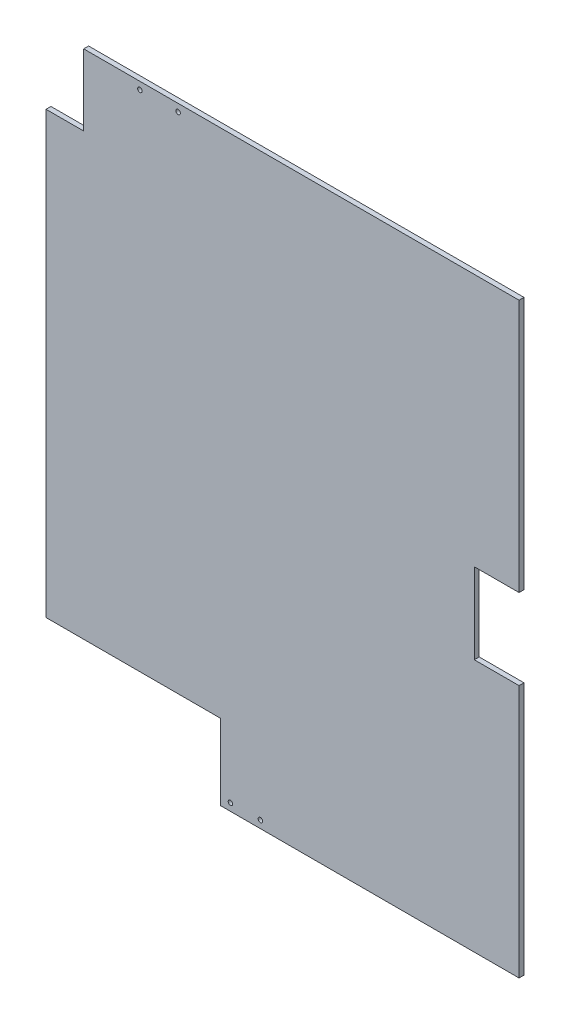
SolidWorks part; units mm, degrees
material "Balsa"
ref_plane "Front Plane" through (0, 0, 0) normal (0, 0, 1) x (1, 0, 0)
ref_plane "Top Plane" through (0, 0, 0) normal (0, 1, 0) x (1, 0, 0)
ref_plane "Right Plane" through (0, 0, 0) normal (1, 0, 0) x (0, 0, -1)
sketch "Sketch1" plane through (0, 0, 0) normal (0, 0, 1) x (1, 0, 0)
  line L0 (-5.7823, -13) -> (25.5, -13)
  line L2 (-5.7823, 1) -> (-5.7823, -13)
  line L5 (24.5, -14) -> (-24.5, -14) construction
  line L6 (342.5, -265) -> (342.5, 30)
  line L7 (-5.8246, -265) -> (65.6329, -265)
  line L8 (-5.8246, -265) -> (-5.8246, -225)
  line L11 (-5.8246, -265) -> (65.6329, -225) construction
  line L12 (-5.8246, -225) -> (65.6329, -265) construction
  line L15 (342.5, -265) -> (25.5, -265)
  line L16 (25.5, 1) -> (25.5, -265)
  line L17 (-5.8246, -225) -> (25.5, -225)
  line L18 (-24.5, -224) -> (24.5, -224) construction
  line L19 (-5.7823, 1) -> (25.5, 1)
  line L20 (24.5, -224) -> (24.5, -14) construction
  line L21 (-85.1981, 31) -> (50.7481, 31) construction
  line L23 (25.5, 1) -> (25.5, 30)
  line L24 (25.5, 30) -> (342.5, 30)
  line L28 (26.2777, -266) -> (-26.2882, -266) construction
  line L30 (-63.4467, 81) -> (255.5737, 81) construction
  line L31 (50.7481, 30) -> (342.5, 30)
  line L32 (50.7481, 30) -> (50.7481, 77.7)
  line L33 (50.7481, 77.7) -> (342.5, 77.7)
  line L34 (342.5, 30) -> (342.5, 77.7)
  line L35 (50.7481, 30) -> (342.5, 77.7) construction
  line L36 (50.7481, 77.7) -> (342.5, 30) construction
  line L37 (255.5737, -319) -> (-63.4467, -319) construction
  line L38 (342.5, -265) -> (142.5, -265)
  line L39 (342.5, -265) -> (342.5, -315.7)
  line L40 (342.5, -315.7) -> (142.5, -315.7)
  line L41 (142.5, -265) -> (142.5, -315.7)
  line L42 (342.5, -265) -> (142.5, -315.7) construction
  line L43 (342.5, -315.7) -> (142.5, -265) construction
  line L44 (50.7481, 31) -> (50.7481, -269) construction
  point P4 (32.4695, -6)
  point P10 (29.9042, -245)
  point P15 (48.1318, -132)
  point P24 (48.1318, 15.5)
  point P36 (196.6241, 53.85)
  point P42 (242.5, -290.35)
  dimension "D1" = 1
  dimension "D2" = 1
  dimension "D3" = 1
  dimension "D4" = 1
  dimension "D5" = 1
  dimension "D6" = 31.3246
  dimension "D7" = 317
  dimension "D8" = 3.3
  dimension "D9" = 200
  dimension "D10" = 3.3
extrude "Boss-Extrude1" add sketch "Sketch1" along normal blind 3.3 contours L24 L23 L16 L7 L15 L6 | L19 L2 L0 L16 | L17 L8 L7 L16 | L24 L34 L33 L32 | L15 L41 L40 L39 region at (9.8589, -6, 0) region at (184, -117.5, 0) region at (9.8377, -245, 0) region at (196.6241, 53.85, 0) region at (242.5, -290.35, 0)
sketch "Sketch2" plane through (0, 0, 0) normal (0, 0, -1) x (-1, 0, 0)
  circle A0 centre (-113.9984, 72.7) radius 1.5
  circle A1 centre (-88.397, 72.7) radius 1.5
  circle A2 centre (-169.1689, -310.7) radius 1.5
  circle A3 centre (-149.0844, -310.7) radius 1.5
  dimension "D1" = 3
  dimension "D2" = 3
  dimension "D3" = 3
  dimension "D4" = 3
extrude "Cut-Extrude1" cut sketch "Sketch2" against normal through all
sketch "Sketch3" plane through (119.3915, 0, 256.0358) normal (0.4226, 0, 0.9063) x (0.9063, 0, -0.4226)
  line L1 (293.4595, -146) -> (268.9595, -146)
  line L2 (293.4595, -146) -> (293.4595, -92)
  line L3 (293.4595, -92) -> (268.9595, -92)
  line L4 (268.9595, -146) -> (268.9595, -92)
  line L5 (293.4595, -146) -> (268.9595, -92) construction
  line L6 (293.4595, -92) -> (268.9595, -146) construction
  point P4 (281.2095, -119)
sketch "Sketch4" plane through (0, 0, 0) normal (0, 0, -1) x (-1, 0, 0)
  line L1 (-342.5, -92) -> (-312.5, -92)
  line L2 (-342.5, -92) -> (-342.5, -146)
  line L3 (-342.5, -146) -> (-312.5, -146)
  line L4 (-312.5, -92) -> (-312.5, -146)
  line L5 (-342.5, -92) -> (-312.5, -146) construction
  line L6 (-342.5, -146) -> (-312.5, -92) construction
  line L7 (-342.5, -315.7) -> (-342.5, 77.7) construction
  point P4 (-327.5, -119)
  dimension "D1" = 54
  dimension "D2" = 30
extrude "Cut-Extrude3" cut sketch "Sketch4" against normal blind 10
sketch "Sketch5" plane through (0, 0, 0) normal (0, 0, -1) x (-1, 0, 0)
  line L0 (5.7823, 1) -> (-25.5, 1) construction
  line L1 (5.8246, -265) -> (-25.5, -265)
  line L2 (5.8246, -265) -> (5.8246, 1)
  line L3 (5.8246, 1) -> (-25.5, 1)
  line L4 (-25.5, -265) -> (-25.5, 1)
  line L5 (5.8246, -265) -> (-25.5, 1) construction
  line L6 (5.8246, 1) -> (-25.5, -265) construction
  line L7 (-25.5, 1) -> (-25.5, 30) construction
  point P4 (-9.8377, -132)
extrude "Cut-Extrude4" cut sketch "Sketch5" against normal blind 10
